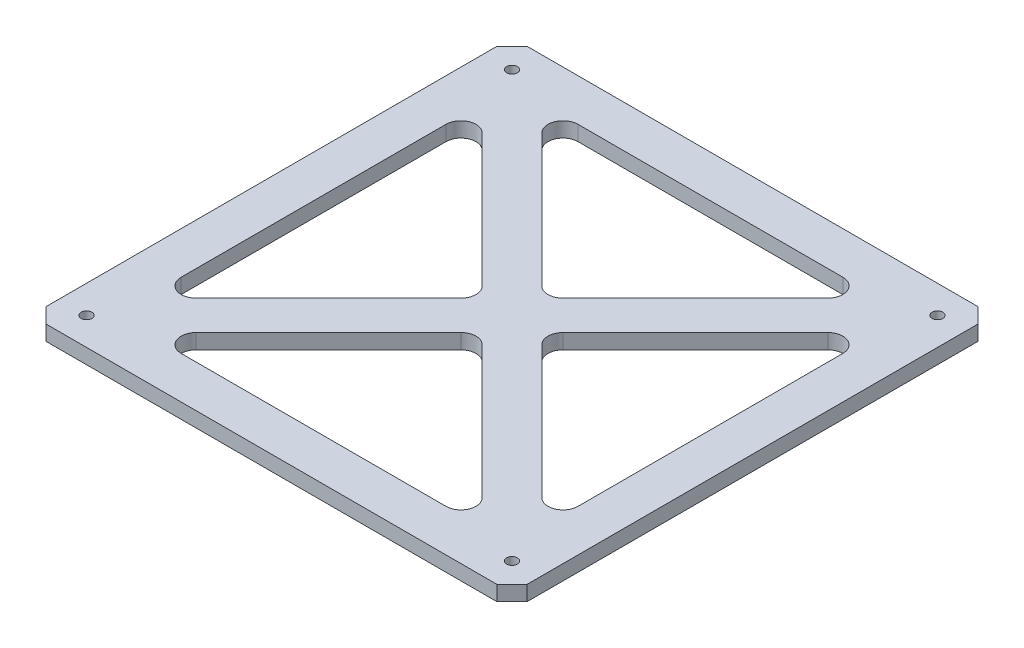
SolidWorks part; units mm, degrees
ref_plane "Front Plane" through (0, 0, 0) normal (0, 0, 1) x (1, 0, 0)
ref_plane "Top Plane" through (0, 0, 0) normal (0, 1, 0) x (1, 0, 0)
ref_plane "Right Plane" through (0, 0, 0) normal (1, 0, 0) x (0, 0, -1)
sketch "Sketch1" plane through (0, 0, 0) normal (0, 1, 0) x (1, 0, 0)
  line L0 (0, 196.85) -> (6.35, 203.2)
  line L1 (6.35, 0) -> (196.85, 0)
  line L2 (0, 6.35) -> (0, 196.85)
  line L3 (6.35, 203.2) -> (196.85, 203.2)
  line L4 (203.2, 6.35) -> (203.2, 196.85)
  line L5 (196.85, 203.2) -> (203.2, 196.85)
  line L6 (196.85, 0) -> (203.2, 6.35)
  line L7 (0, 6.35) -> (6.35, 0)
  point P0 (0, 0)
  point P1 (203.2, 203.2)
  point P2 (0, 203.2)
  point P3 (203.2, 0)
  dimension "D1" = 203.2
  dimension "D2" = 203.2
extrude "Boss-Extrude1" add sketch "Sketch1" along normal blind 6.35
sketch "Sketch2" plane through (0, 6.35, 0) normal (0, 1, 0) x (1, 0, 0)
  line L0 (203.2, 6.35) -> (203.2, 196.85) construction
  line L1 (45.6826, 185.42) -> (157.5174, 185.42)
  line L2 (17.78, 157.5174) -> (17.78, 45.6826)
  line L3 (45.6826, 17.78) -> (157.5174, 17.78)
  line L4 (185.42, 157.5174) -> (185.42, 45.6826)
  line L5 (196.85, 203.2) -> (6.35, 203.2) construction
  line L6 (0, 196.85) -> (0, 6.35) construction
  line L7 (3.175, 3.175) -> (200.025, 200.025) construction
  line L8 (3.175, 200.025) -> (101.6, 101.6) construction
  line L9 (28.6201, 162.0075) -> (84.5375, 106.0901)
  line L10 (41.1925, 28.6201) -> (97.1099, 84.5375)
  line L11 (41.1925, 174.5799) -> (97.1099, 118.6625)
  line L12 (28.6201, 41.1925) -> (84.5375, 97.1099)
  line L13 (9.4612, -3.1112) -> (206.3112, 193.7388) construction
  line L14 (-3.1112, 9.4612) -> (193.7388, 206.3112) construction
  line L15 (9.4612, 206.3112) -> (206.3112, 9.4612) construction
  line L16 (-3.1112, 193.7388) -> (193.7388, -3.1112) construction
  line L17 (118.6625, 106.0901) -> (174.5799, 162.0075)
  line L18 (101.6, 101.6) -> (200.025, 3.175) construction
  line L19 (3.175, 200.025) -> (200.025, 3.175) construction
  line L20 (118.6625, 97.1099) -> (174.5799, 41.1925)
  line L21 (106.0901, 118.6625) -> (162.0075, 174.5799)
  line L22 (106.0901, 84.5375) -> (162.0075, 28.6201)
  line L23 (6.35, 0) -> (196.85, 0) construction
  line L24 (6.35, 203.2) -> (0, 196.85) construction
  line L25 (203.2, 196.85) -> (196.85, 203.2) construction
  line L26 (196.85, 0) -> (203.2, 6.35) construction
  arc A0 (185.42, 45.6826) -> (174.5799, 41.1925) centre (179.07, 45.6826) cw
  arc A1 (185.42, 157.5174) -> (174.5799, 162.0075) centre (179.07, 157.5174) ccw
  arc A2 (157.5174, 185.42) -> (162.0075, 174.5799) centre (157.5174, 179.07) cw
  arc A3 (118.6625, 106.0901) -> (118.6625, 97.1099) centre (123.1526, 101.6) ccw
  arc A4 (41.1925, 28.6201) -> (45.6826, 17.78) centre (45.6826, 24.13) ccw
  arc A5 (157.5174, 17.78) -> (162.0075, 28.6201) centre (157.5174, 24.13) ccw
  arc A6 (28.6201, 41.1925) -> (17.78, 45.6826) centre (24.13, 45.6826) cw
  arc A7 (84.5375, 97.1099) -> (84.5375, 106.0901) centre (80.0474, 101.6) ccw
  arc A8 (28.6201, 162.0075) -> (17.78, 157.5174) centre (24.13, 157.5174) ccw
  arc A9 (41.1925, 174.5799) -> (45.6826, 185.42) centre (45.6826, 179.07) cw
  arc A10 (97.1099, 84.5375) -> (106.0901, 84.5375) centre (101.6, 80.0474) cw
  arc A11 (97.1099, 118.6625) -> (106.0901, 118.6625) centre (101.6, 123.1526) ccw
  point P10 (0, 101.6)
  point P11 (17.78, 101.6)
  point P37 (101.6, 17.78)
  point P40 (101.6, 101.6)
  point P50 (114.1724, 101.6)
  point P65 (101.6, 89.0276)
  point P68 (101.6, 114.1724)
  dimension "D7" = 6.35
  dimension "D8" = 6.35
  dimension "D9" = 6.35
  dimension "D1" = 17.78
  dimension "D2" = 17.78
  dimension "D3" = 8.89
  dimension "D5" = 17.78
  dimension "D6" = 17.78
  dimension "D4" = 8.89
extrude "Cut-Extrude1" cut sketch "Sketch2" against normal through all
sketch "Sketch3" plane through (0, 6.35, 0) normal (0, 1, 0) x (1, 0, 0)
  line L0 (6.35, 0) -> (196.85, 0) construction
  line L1 (0, 196.85) -> (0, 6.35) construction
  line L2 (203.2, 6.35) -> (203.2, 196.85) construction
  line L3 (196.85, 203.2) -> (6.35, 203.2) construction
  circle A0 centre (11.7373, 11.7373) radius 2.286
  circle A1 centre (191.4627, 11.7373) radius 2.286
  circle A2 centre (191.4627, 191.4627) radius 2.286
  circle A3 centre (11.7373, 191.4627) radius 2.286
  dimension "D1" = 2
  dimension "D3" = 4.572
  dimension "D4" = 11.7373
  dimension "D5" = 11.7373
  dimension "D6" = 11.7373
  dimension "D7" = 11.7373
  dimension "D8" = 11.7373
  dimension "D2" = 2
extrude "Cut-Extrude2" cut sketch "Sketch3" against normal through all
